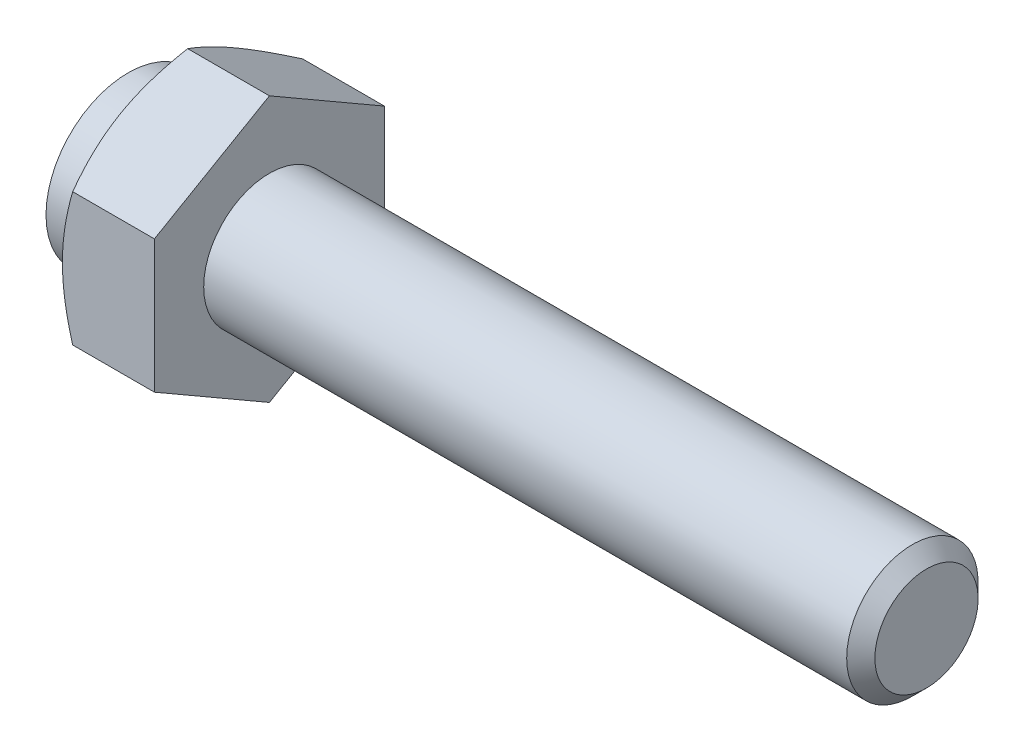
SolidWorks part; units mm, degrees
ref_plane "前视基准面" through (0, 0, 0) normal (0, 0, 1) x (1, 0, 0)
ref_plane "上视基准面" through (0, 0, 0) normal (0, 1, 0) x (1, 0, 0)
ref_plane "右视基准面" through (0, 0, 0) normal (1, 0, 0) x (0, 0, -1)
sketch "草图1" plane through (0, 0, 0) normal (0, 0, 1) x (1, 0, 0)
  line L0 (-4.3, 0) -> (-4.3, 2.5)
  line L1 (-4.3, 2.5) -> (-2.8, 2.5)
  line L2 (-2.8, 2.5) -> (-2.8, 3.5)
  line L3 (-2.8, 3.5) -> (-2.3959, 4.2)
  line L4 (-2.3959, 4.2) -> (0, 4.2)
  line L5 (0, 4.2) -> (0, 2)
  line L6 (0, 2) -> (19.5705, 2)
  line L7 (19.5705, 2) -> (20, 1.5705)
  line L8 (20, 1.5705) -> (20, 0)
  line L9 (20, 0) -> (-4.3, 0)
  line L10 (20, 0) -> (-4.3, 0) construction
revolve "旋转1" add sketch "草图1" angle 360 about L10 reverse direction yes
cosmetic thread "装饰螺纹线1" parameters "D1"=18.6, "D2"=3.141
ref_plane "基准面1" through (10, 0, 0) normal (1, 0, 0) x (0, 0, -1)
ref_plane "基准面2" through (20, 0, 0) normal (1, 0, 0) x (0, 0, -1)
sketch "草图2" plane through (0, 0, 0) normal (1, 0, 0) x (0, 0, -1)
  line L0 (-8.1, -8.1) -> (8.1, -8.1)
  line L1 (8.1, -8.1) -> (8.1, 8.1)
  line L2 (8.1, 8.1) -> (-8.1, 8.1)
  line L3 (-8.1, 8.1) -> (-8.1, -8.1)
  line L4 (-3.5, 2.0207) -> (-3.5, -2.0207)
  line L5 (-3.5, -2.0207) -> (0, -4.0415)
  line L6 (0, -4.0415) -> (3.5, -2.0207)
  line L7 (3.5, -2.0207) -> (3.5, 2.0207)
  line L8 (3.5, 2.0207) -> (0, 4.0415)
  line L9 (0, 4.0415) -> (-3.5, 2.0207)
extrude "切除-拉伸1" cut sketch "草图2" against normal blind 4.3
ref_plane "基准面3" through (-4.3, 0, 0) normal (1, 0, 0) x (0, 0, -1)
ref_plane "ustb_n XY" through (10, 0, 0) normal (1, 0, 0) x (0, 0, -1)
ref_plane "ustb_n XZ" through (0, 0, 0) normal (0, -1, 0) x (1, 0, 0)
ref_plane "ustb_n YZ" through (0, 0, 0) normal (0, 0, -1) x (-1, 0, 0)
ref_axis "ustb_n X" through (10, 0, 80.9) along (0, 0, -1)
ref_axis "ustb_n Y" through (10, -50, 0) along (0, 1, 0)
ref_axis "ustb_n Z" through (80.9, 0, 0) along (-1, 0, 0)
sketch3d "ustb_n"
  point P0 (10, 0, 0)
ref_plane "cp XY" through (-4.3, 0, 0) normal (1, 0, 0) x (0, 0, -1)
ref_plane "cp XZ" through (0, 0, 0) normal (0, -1, 0) x (1, 0, 0)
ref_plane "cp YZ" through (0, 0, 0) normal (0, 0, -1) x (-1, 0, 0)
ref_axis "cp X" through (-4.3, 0, 80.9) along (0, 0, -1)
ref_axis "cp Y" through (-4.3, -50, 0) along (0, 1, 0)
ref_axis "cp Z" through (80.9, 0, 0) along (-1, 0, 0)
sketch3d "cp"
  point P0 (-4.3, 0, 0)
